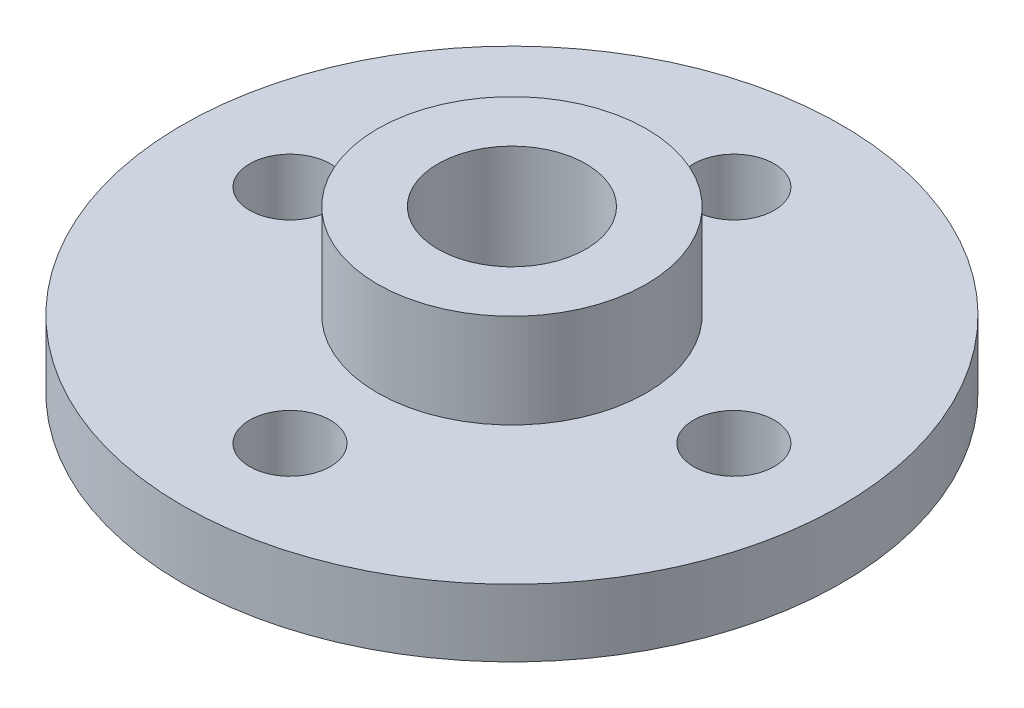
SolidWorks part; units mm, degrees
material "6063-O"
ref_plane "Спереди" through (0, 0, 0) normal (0, 0, 1) x (1, 0, 0)
ref_plane "Сверху" through (0, 0, 0) normal (0, 1, 0) x (1, 0, 0)
ref_plane "Справа" through (0, 0, 0) normal (1, 0, 0) x (0, 0, -1)
sketch "Эскиз1" plane through (0, 0, 0) normal (0, 1, 0) x (1, 0, 0)
  circle A0 centre (0, 0) radius 12.25
  circle A2 centre (0, 0) radius 5
  dimension "D2" = 24.5
  dimension "D3" = 10
extrude "Бобышка-Вытянуть1" add sketch "Эскиз1" along normal blind 2.5 contours A0
extrude "Бобышка-Вытянуть2" add sketch "Эскиз1<3>" along normal blind 6 contours A2
sketch "Эскиз1<3>" plane through (0, 0, 0) normal (0, 1, 0) x (1, 0, 0) same geometry as "Эскиз1"
sketch "Эскиз2" plane through (0, 0, 0) normal (0, 1, 0) x (1, 0, 0)
  circle A0 centre (0, 0) radius 8.25 construction
  circle A1 centre (0, 0) radius 1.5
  circle A2 centre (8.25, 0) radius 1.5
  circle A3 centre (0, -8.25) radius 1.5
  circle A4 centre (-8.25, 0) radius 1.5
  circle A5 centre (0, 8.25) radius 1.5
  circle A6 centre (0, 0) radius 2.75
  point P15 (0, 0)
  dimension "D1" = 16.5
  dimension "D2" = 3
  dimension "D3" = 4
extrude "Вырез-Вытянуть2" cut sketch "Эскиз2" along normal blind 6 contours A1 | A4 | A5 | A2 | A3 region at (0, 0, 0) region at (8.25, 0, 0) region at (0, 0, 8.25) region at (-8.25, 0, 0) region at (0, 0, -8.25)
extrude "Вырез-Вытянуть3" cut sketch "Эскиз2<3>" against normal blind 4 from surface contours A6 starting at face at (0, 6, 1.5)
sketch "Эскиз2<3>" plane through (0, 0, 0) normal (0, 1, 0) x (1, 0, 0) same geometry as "Эскиз2"
